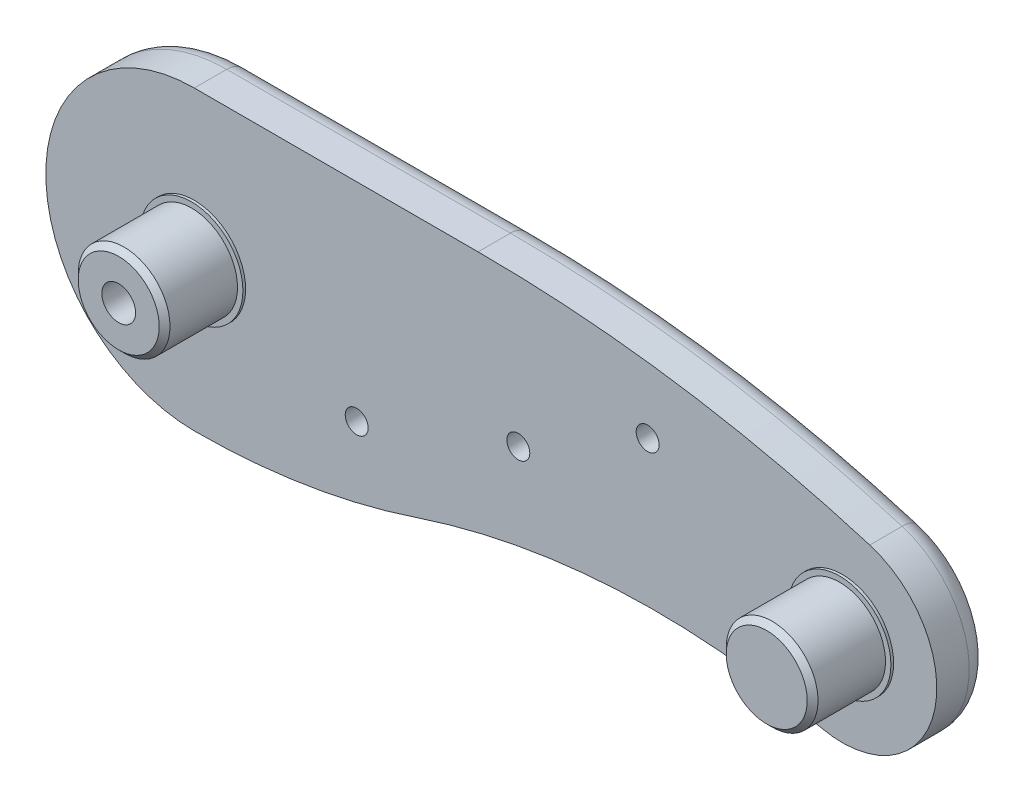
SolidWorks part; units mm, degrees
ref_plane "Front Plane" through (0, 0, 0) normal (0, 0, 1) x (1, 0, 0)
ref_plane "Top Plane" through (0, 0, 0) normal (0, 1, 0) x (1, 0, 0)
ref_plane "Right Plane" through (0, 0, 0) normal (1, 0, 0) x (0, 0, -1)
sketch "Sketch1" plane through (0, 0, 0) normal (0, 0, 1) x (1, 0, 0)
  line L0 (0, 27.5) -> (52.5463, 27.5)
  line L1 (0, 0) -> (120, 0) construction
  line L2 (0, 0) -> (0, -27.5) construction
  circle A0 centre (0, 0) radius 27.5
  circle A1 centre (120, 0) radius 17.5
  arc A2 (52.5463, 27.5) -> (125.0772, 16.7473) centre (52.5463, -222.5) cw
  arc A3 (116.1527, -17.0719) -> (41.1063, -20.8299) centre (85.3746, -153.6468) ccw
  arc A4 (0, -27.5) -> (41.1063, -20.8299) centre (0, 102.5) ccw
  dimension "D1" = 55
  dimension "D3" = 35
  dimension "D4" = 130
  dimension "D5" = 140
  dimension "D6" = 250
  dimension "D2" = 120
extrude "Boss-Extrude1" add sketch "Sketch1" along normal blind 6 contours A0 A4 A3 A1 A2 L0 | A0 | A1 region at (61.3869, 4.6825, 0) region at (0, 0, 0) region at (120, 0, 0)
sketch "Sketch3" plane through (0, 0, 0) normal (0, 0, -1) x (-1, 0, 0)
  circle A0 centre (0, 0) radius 10
  circle A1 centre (0, 0) radius 27.5
  arc A2 (0, -27.5) -> (0, 27.5) centre (0, 0) ccw construction
  line M1 (0, 27.5) -> (-52.5463, 27.5)
  arc M2 (-52.5463, 27.5) -> (-125.0772, 16.7473) centre (-52.5463, -222.5) ccw
  arc M3 (-125.0772, 16.7473) -> (-116.1527, -17.0719) centre (-120, 0) ccw
  arc M4 (-116.1527, -17.0719) -> (-41.1063, -20.8299) centre (-85.3746, -153.6468) cw
  arc M5 (-41.1063, -20.8299) -> (0, -27.5) centre (0, 102.5) ccw
  arc M6 (0, -27.5) -> (0, 27.5) centre (0, 0) ccw
  dimension "D1" = 20
extrude "Boss-Extrude3" add sketch "Sketch3" along normal blind 4 contours A1 M1 M2 M3 M4 M5 | A1 A0 M6 region at (-18.8954, -18.8954, 0) region at (73.4928, 3.7154, 0)
sketch "Sketch4" plane through (0, 0, 6) normal (0, 0, 1) x (1, 0, 0)
  circle A0 centre (0, 0) radius 8.5
  circle A1 centre (120, 0) radius 8.5
  dimension "D1" = 17
  dimension "D2" = 17
extrude "Boss-Extrude4" add sketch "Sketch4" along normal blind 14
sketch "Sketch5" plane through (0, 0, -4) normal (0, 0, -1) x (-1, 0, 0)
  line L0 (0, 0) -> (-60, 0) construction
  line L1 (0, 0) -> (-83.9535, 13.2969) construction
  line L2 (0, 0) -> (-30.0702, -10.9446) construction
  circle A0 centre (-83.9535, 13.2969) radius 2.125
  circle A1 centre (-60, 0) radius 2.125
  circle A2 centre (-30.0702, -10.9446) radius 2.125
  dimension "D6" = 4.25
  dimension "D1" = 20
  dimension "D2" = 9
  dimension "D3" = 85
  dimension "D4" = 60
  dimension "D5" = 32
extrude "Cut-Extrude1" cut sketch "Sketch5" against normal through all
sketch "Sketch6" plane through (0, 0, -4) normal (0, 0, -1) x (-1, 0, 0)
  circle A0 centre (-83.9535, 13.2969) radius 3.75
  circle A1 centre (-60, 0) radius 3.75
  circle A2 centre (-30.0702, -10.9446) radius 3.75
  dimension "D1" = 7.5
extrude "Cut-Extrude2" cut sketch "Sketch6" against normal blind 4.25
fillet "Fillet1" radius 4 6 edges at (-27.5, 0, -4) (20.822, -25.8216, -4) (78.3727, -13.822, -4) (136.9208, -4.4652, -4) (89.2081, 24.7972, -4) (26.2732, 27.5, -4)
sketch "Sketch7" plane through (0, 0, 6) normal (0, 0, 1) x (1, 0, 0)
  circle A0 centre (0, 0) radius 9.5
  circle A1 centre (0, 0) radius 8.5 construction
  circle A2 centre (120, 0) radius 9.5
  circle A3 centre (0, 0) radius 8.5
  circle A4 centre (0, 0) radius 8.5
  circle A5 centre (120, 0) radius 8.5 construction
  circle A6 centre (120, 0) radius 8.5
  dimension "D1" = 1
  dimension "D3" = 1
  dimension "D2" = 0
extrude "Boss-Extrude5" add sketch "Sketch7" along normal blind 0.5
chamfer "Chamfer2" distance 1 angle 45 2 edges at (8.5, 0, 20) (128.5, 0, 20)
sketch "Sketch8" plane through (0, 0, 0) normal (0, 0, -1) x (-1, 0, 0)
  circle A0 centre (0, 0) radius 1.625
  dimension "D1" = 3.25
extrude "Cut-Extrude3" cut sketch "Sketch8" against normal through all
sketch "Sketch9" plane through (0, 0, 20) normal (0, 0, 1) x (1, 0, 0)
  circle A0 centre (0, 0) radius 3.125
  dimension "D1" = 6.25
extrude "Cut-Extrude4" cut sketch "Sketch9" against normal blind 17
sketch "Sketch10" plane through (0, 0, 0) normal (0, 0, -1) x (-1, 0, 0)
  line L0 (0, 0) -> (0, 7.42) construction
  circle A0 centre (0, 0) radius 7.42 construction
  circle A1 centre (0, 7.42) radius 1
  circle A2 centre (7.42, 0) radius 1
  circle A3 centre (0, -7.42) radius 1
  circle A4 centre (-7.42, 0) radius 1
  point P5 (0, 0)
  point P6 (0, 0)
  point P14 (0, 0)
  dimension "D1" = 14.84
  dimension "D2" = 2
  dimension "D3" = 4
extrude "Cut-Extrude5" cut sketch "Sketch10" against normal blind 4
sketch "Sketch11" plane through (0, 0, -4) normal (0, 0, -1) x (-1, 0, 0)
  circle A0 centre (0, 0) radius 14
  circle A1 centre (0, 0) radius 10 construction
  circle A2 centre (0, 0) radius 10
  dimension "D1" = 4
extrude "Boss-Extrude6" add sketch "Sketch11" along normal blind 2
chamfer "Chamfer3" distance 4 angle 45 1 edges at (-14, 0, -4)
